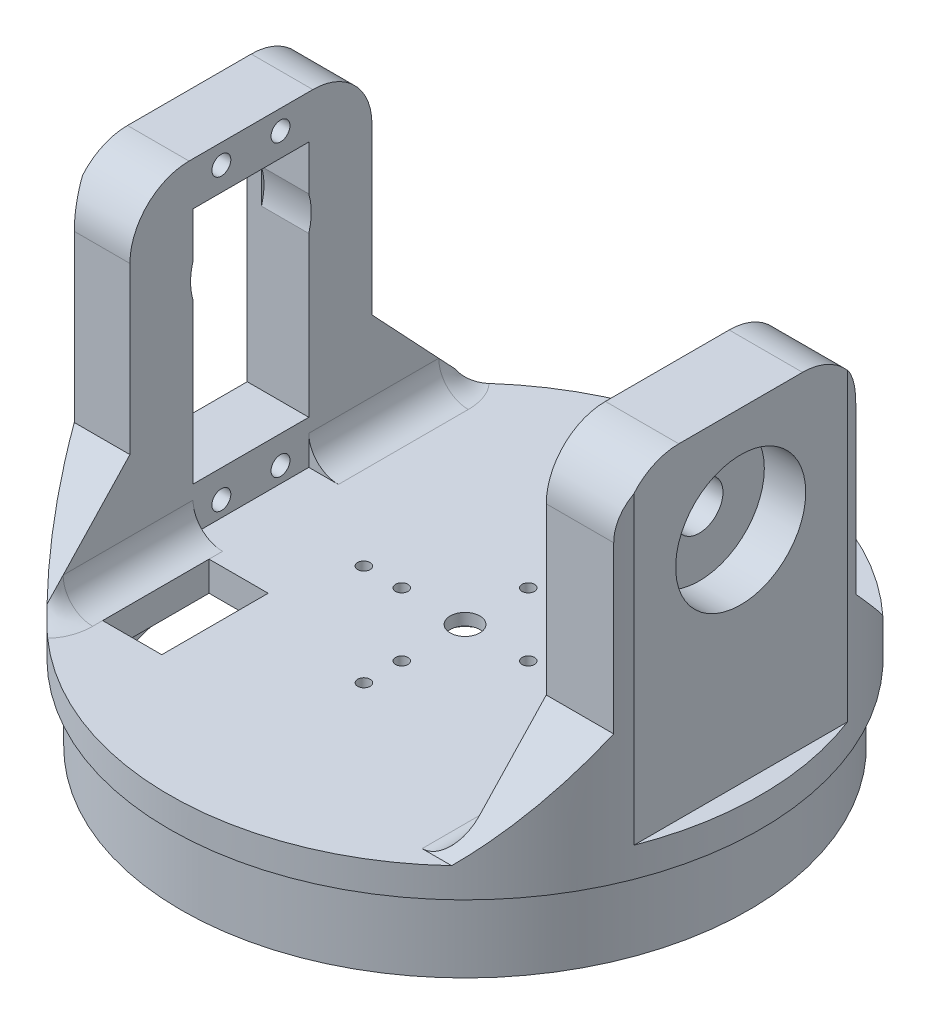
SolidWorks part; units mm, degrees
ref_plane "Front Plane" through (0, 0, 0) normal (0, 0, 1) x (1, 0, 0)
ref_plane "Top Plane" through (0, 0, 0) normal (0, 1, 0) x (1, 0, 0)
ref_plane "Right Plane" through (0, 0, 0) normal (1, 0, 0) x (0, 0, -1)
sketch "Sketch2" plane through (0, 0, 0) normal (0, 1, 0) x (1, 0, 0)
  circle A0 centre (0, 0) radius 50
  dimension "D1" = 100
extrude "Boss-Extrude1" add sketch "Sketch2" along normal blind 5
sketch "Sketch5" plane through (0, 0, 0) normal (0, -1, 0) x (1, 0, 0)
  line L4 (-19.5, 4.3) -> (-4.3, 4.3)
  line L6 (-4.3, 19.5) -> (-4.3, 4.3)
  line L9 (4.3, -19.5) -> (4.3, -4.3)
  line L10 (19.5, -4.3) -> (4.3, -4.3)
  line L12 (4.3, 19.5) -> (4.3, 4.3)
  line L14 (19.5, 4.3) -> (4.3, 4.3)
  line L16 (-19.5, -4.3) -> (-4.3, -4.3)
  line L18 (-4.3, -19.5) -> (-4.3, -4.3)
  arc A0 (-19.5, -4.3) -> (-19.5, 4.3) centre (-19.5, 0) cw
  arc A1 (-4.3, 19.5) -> (4.3, 19.5) centre (0, 19.5) cw
  arc A2 (19.5, 4.3) -> (19.5, -4.3) centre (19.5, 0) cw
  arc A3 (4.3, -19.5) -> (-4.3, -19.5) centre (0, -19.5) cw
  dimension "D1" = 8.6
  dimension "D2" = 8.6
  dimension "D3" = 8.6
  dimension "D4" = 15.2
  dimension "D5" = 15.2
  dimension "D6" = 15.2
  dimension "D7" = 15.2
  dimension "D8" = 8.6
extrude "Cut-Extrude2" cut sketch "Sketch5" against normal blind 2.15
fillet "Fillet3" radius 4 4 edges at (4.3, 1.075, -4.3) (-4.3, 1.075, -4.3) (4.3, 1.075, 4.3) (-4.3, 1.075, 4.3)
sketch "Sketch6" plane through (0, 5, 0) normal (0, 1, 0) x (1, 0, 0)
  line L2 (34.2081, -36.4665) -> (34.2081, 36.4665)
  line L3 (46.6228, -18.0642) -> (46.6228, 18.0642)
  line L4 (-34.2081, -36.4665) -> (-34.2081, 36.4665)
  line L6 (-46.6228, -18.0642) -> (-46.6228, 18.0642)
  circle A0 centre (0, 0) radius 50 construction
  arc A1 (-34.2081, 36.4665) -> (-46.6228, 18.0642) centre (0, 0) ccw
  arc A2 (34.2081, -36.4665) -> (46.6228, -18.0642) centre (0, 0) ccw
  arc A3 (-46.6228, -18.0642) -> (-34.2081, -36.4665) centre (0, 0) ccw
  arc A4 (46.6228, 18.0642) -> (34.2081, 36.4665) centre (0, 0) ccw
  point P0 (0, 0)
  dimension "D1" = 36.1285
extrude "Boss-Extrude2" add sketch "Sketch6" along normal blind 55
sketch "Sketch7" plane through (-34.2081, 0, 0) normal (1, 0, 0) x (0, 0, -1)
  line L1 (0, 60) -> (0, 5)
  line L2 (-36.4665, 60) -> (36.4665, 60) construction
  line L3 (-36.4665, 5) -> (36.4665, 5) construction
  line L4 (36.4665, 60) -> (36.4665, 5) construction
  line L5 (9.79, 12.34) -> (-9.79, 12.34)
  line L6 (9.79, 12.34) -> (9.79, 52.66)
  line L9 (9.79, 52.66) -> (-9.79, 52.66)
  line L10 (-9.79, 12.34) -> (-9.79, 52.66)
  line L11 (9.79, 12.34) -> (-9.79, 52.66) construction
  line L12 (9.79, 52.66) -> (-9.79, 12.34) construction
  point P6 (0, 32.5)
  dimension "D1" = 40.32
  dimension "D2" = 36.4665
  dimension "D3" = 19.58
extrude "Cut-Extrude3" cut sketch "Sketch7" against normal blind 50 contours L10 L9 L6 L5
sketch "Sketch8" plane through (-34.2081, 0, 0) normal (1, 0, 0) x (0, 0, -1)
  line L0 (9.79, 52.66) -> (-9.79, 52.66) construction
  line L1 (-9.79, 12.34) -> (-9.79, 52.66) construction
  circle A0 centre (0, 42.17) radius 4
  dimension "D1" = 8
  dimension "D2" = 10.49
  dimension "D3" = 9.79
sketch "Sketch9" plane through (-34.2081, 0, 0) normal (1, 0, 0) x (0, 0, -1)
  line L0 (-36.4665, 60) -> (-36.4665, 5) construction
  line L2 (-36.4665, 5) -> (36.4665, 5) construction
  line L3 (-36.4665, 22) -> (-20.4665, 22)
  line L6 (36.4665, 60) -> (36.4665, 22)
  line L7 (-20.4665, 22) -> (-20.4665, 60)
  line L8 (-36.4665, 60) -> (36.4665, 60) construction
  line L9 (20.4665, 60) -> (36.4665, 60)
  line L10 (20.4665, 22) -> (20.4665, 60)
  line L11 (-20.4665, 60) -> (-36.4665, 60)
  line L12 (36.4665, 22) -> (20.4665, 22)
  line L13 (-36.4665, 60) -> (-36.4665, 22)
  dimension "D1" = 17
  dimension "D2" = 16
extrude "Cut-Extrude5" cut sketch "Sketch9" against normal blind 18.45 and the other way blind 103
fillet "Fillet6" radius 10 4 edges at (-39.9137, 60, -20.4665) (-39.9137, 60, 20.4665) (39.9137, 60, 20.4665) (39.9137, 60, -20.4665)
sketch "Sketch10" plane through (-34.2081, 0, 0) normal (1, 0, 0) x (0, 0, -1)
  line L0 (-20.4665, 22) -> (-36.4665, 5)
  line L1 (-36.4665, 5) -> (-36.4665, 22)
  line L2 (-36.4665, 22) -> (-20.4665, 22)
  line L3 (0, 12.34) -> (0, 8.4378)
  line L4 (9.79, 12.34) -> (-9.79, 12.34) construction
  line L5 (36.4665, 22) -> (20.4665, 22)
  line L6 (36.4665, 5) -> (36.4665, 22)
  line L7 (20.4665, 22) -> (36.4665, 5)
  line M10 (-20.4665, 22) -> (-36.4665, 22)
  line M11 (-36.4665, 22) -> (-36.4665, 5)
  line M13 (36.4665, 5) -> (36.4665, 22)
  line M14 (36.4665, 22) -> (20.4665, 22)
extrude "Cut-Extrude6" cut sketch "Sketch10" against normal blind 18.45 and the other way blind 98.45 contours L0 M10 M11 | L7 M14 M13 region at (-34.2081, 16.3333, 31.1332) region at (-34.2081, 16.3333, -31.1332)
sketch "Sketch11" plane through (0, 2.15, 0) normal (0, -1, 0) x (1, 0, 0)
  circle A0 centre (0, 0) radius 2.5
  dimension "D1" = 5
extrude "Cut-Extrude7" cut sketch "Sketch11" against normal blind 10
sketch "Sketch23" plane through (0, 0, 0) normal (0, -1, 0) x (1, 0, 0)
  circle A0 centre (0, 0) radius 48
  circle A1 centre (0, 0) radius 45
  dimension "D1" = 90
  dimension "D2" = 96
extrude "Boss-Extrude3" add sketch "Sketch23" along normal blind 12.85
sketch "Sketch15" plane through (0, 2.15, 0) normal (0, -1, 0) x (1, 0, 0)
  circle A0 centre (0, 0) radius 3.6
  dimension "D1" = 7.2
extrude "Cut-Extrude9" cut sketch "Sketch15" against normal blind 0.85
fillet "Fillet7" radius 5 1 edges at (34.2081, 5, 0)
sketch "Sketch17" plane through (46.6228, 0, 0) normal (1, 0, 0) x (0, 0, -1)
  circle A0 centre (0, 42.17) radius 11
  dimension "D1" = 22
extrude "Cut-Extrude11" cut sketch "Sketch17" against normal blind 7
extrude "Cut-Extrude12" cut sketch "Sketch8" along normal blind 114
sketch "Sketch20" plane through (-34.2081, 0, 0) normal (1, 0, 0) x (0, 0, -1)
  line L1 (-36.4665, 5) -> (46.8417, 5)
  line L2 (-36.4665, 5) -> (-36.4665, 69.1867)
  line L3 (-36.4665, 69.1867) -> (46.8417, 69.1867)
  line L4 (46.8417, 5) -> (46.8417, 69.1867)
extrude "Cut-Extrude14" cut sketch "Sketch20" against normal blind 2
fillet "Fillet8" radius 5 1 edges at (-36.2081, 5, 0)
sketch "Sketch21" plane through (-36.2081, 0, 0) normal (1, 0, 0) x (0, 0, -1)
  line L1 (-9.79, 15) -> (9.79, 15)
  line L2 (-9.79, 15) -> (-9.79, 5)
  line L3 (-9.79, 5) -> (9.79, 5)
  line L4 (9.79, 15) -> (9.79, 5)
  dimension "D1" = 19.58
  dimension "D2" = 10
extrude "Cut-Extrude15" cut sketch "Sketch21" along normal blind 11
sketch "Sketch22" plane through (0, 5, 0) normal (0, 1, 0) x (1, 0, 0)
  line L0 (-31.2081, -9.79) -> (-31.2081, -36.4665) construction
  line L1 (-31.2081, -12.0808) -> (-21.2081, -12.0808)
  line L2 (-31.2081, -12.0808) -> (-31.2081, -30.0808)
  line L3 (-31.2081, -30.0808) -> (-21.2081, -30.0808)
  line L4 (-21.2081, -12.0808) -> (-21.2081, -30.0808)
  dimension "D1" = 10
  dimension "D2" = 18
extrude "Cut-Extrude16" cut sketch "Sketch22" against normal blind 11
sketch "Sketch24" plane through (-46.6228, 0, 0) normal (-1, 0, 0) x (0, 0, 1)
  circle A0 centre (0, 42.17) radius 10.2092
extrude "Cut-Extrude17" cut sketch "Sketch24" along normal blind 8 from surface contours A0 starting at face at (-36.2081, 26.5118, 0)
sketch "Sketch25" plane through (-36.2081, 0, 0) normal (1, 0, 0) x (0, 0, -1)
  circle A0 centre (-5, 56.67) radius 1.6
  circle A1 centre (5, 56.67) radius 1.6
  circle A2 centre (-5, 7.67) radius 1.6
  circle A3 centre (5, 7.67) radius 1.6
extrude "Cut-Extrude18" cut sketch "Sketch25" against normal up to next
sketch "Sketch26" plane through (-46.6228, 0, 0) normal (-1, 0, 0) x (0, 0, 1)
  circle A0 centre (-5, 56.67) radius 2.5
  circle A1 centre (5, 56.67) radius 2.5
extrude "Cut-Extrude20" cut sketch "Sketch26" against normal blind 2.5
sketch "Sketch27" plane through (0, 2.15, 0) normal (0, -1, 0) x (1, 0, 0)
  circle A0 centre (-17.1, 0) radius 1.05
  circle A1 centre (0, 17.1) radius 1.05
  circle A2 centre (0, -17.1) radius 1.05
  circle A3 centre (17.1, 0) radius 1.05
  circle A4 centre (0, 10.7) radius 1.05
  circle A5 centre (0, -10.7) radius 1.05
  circle A6 centre (-10.7, 0) radius 1.05
  circle A7 centre (10.7, 0) radius 1.05
extrude "Cut-Extrude21" cut sketch "Sketch27" against normal up to next
